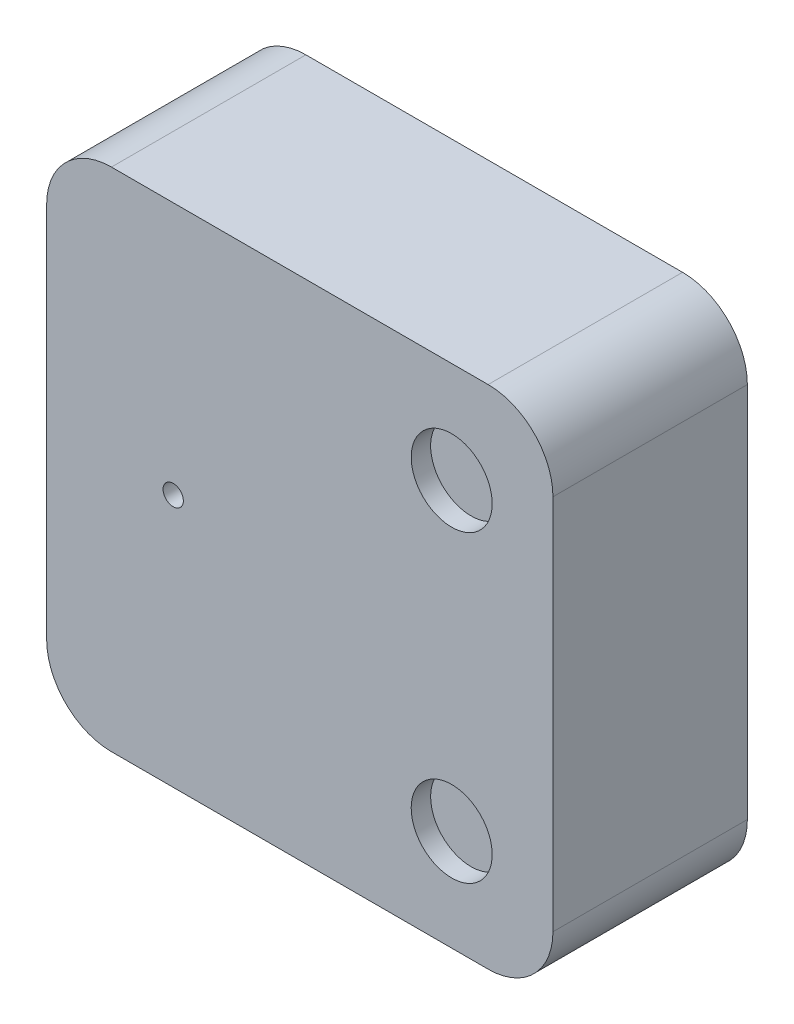
SolidWorks part; units mm, degrees
ref_plane "Plan de face" through (0, 0, 0) normal (0, 0, 1) x (1, 0, 0)
ref_plane "Plan de dessus" through (0, 0, 0) normal (0, 1, 0) x (1, 0, 0)
ref_plane "Plan de droite" through (0, 0, 0) normal (1, 0, 0) x (0, 0, -1)
other "Centre de masse"
sketch "Esquisse1" plane through (0, 0, 0) normal (0, 0, 1) x (1, 0, 0)
  line L1 (-125, -125) -> (125, -125)
  line L2 (-125, -125) -> (-125, 125)
  line L3 (-125, 125) -> (125, 125)
  line L4 (125, -125) -> (125, 125)
  line L5 (-125, -125) -> (125, 125) construction
  line L6 (-125, 125) -> (125, -125) construction
  point P0 (0, 0)
  dimension "D1" = 250
  dimension "D2" = 250
extrude "Boss.-Extru.1" add sketch "Esquisse1" along normal blind 96
fillet "Congé1" radius 32 4 edges at (-125, 125, 48) (-125, -125, 48) (125, -125, 48) (125, 125, 48)
sketch "Esquisse2" plane through (0, 0, 96) normal (0, 0, 1) x (1, 0, 0)
  line L0 (93, 125) -> (-93, 125) construction
  line L1 (2.5426, 0) -> (67.0148, 0) construction
  line L2 (125, -93) -> (125, 93) construction
  line L3 (-125, 35.3964) -> (-125, -5.661) construction
  line L4 (-125, 93) -> (-125, -93) construction
  circle A0 centre (75, 75) radius 20
  circle A1 centre (75, -75) radius 20
  circle A2 centre (-62.5, 0) radius 5
  dimension "D1" = 40
  dimension "D4" = 10
  dimension "D2" = 50
  dimension "D3" = 50
  dimension "D5" = 62.5
  dimension "D6" = 125
extrude "Enlèv. mat.-Extru.1" cut sketch "Esquisse2" against normal blind 9.6
ref_axis "Axe1" through (0, 0, 0) along (0, 0, 1)
ref_point "Point1"
equation "\"L\" = 0.25m"
equation "\"D2@Esquisse1\"=\"L\""
equation "\"D1@Esquisse1\"=\"L\""
equation "\"e\"= 0.096m"
equation "\"D1@Boss.-Extru.1\"=\"e\""
equation "\"D1@Congé1\"=\"e\"/3m"
equation "\"D2@Esquisse2\"=\"L\"/5m"
equation "\"D3@Esquisse2\"=\"L\"/5"
equation "\"D\"= 0.04m"
equation "\"D1@Esquisse2\"=\"D\""
equation "\"D1@Enlèv. mat.-Extru.1\"=\"e\"/10"
equation "\"D5@Esquisse2\"=\"L\"/4"
